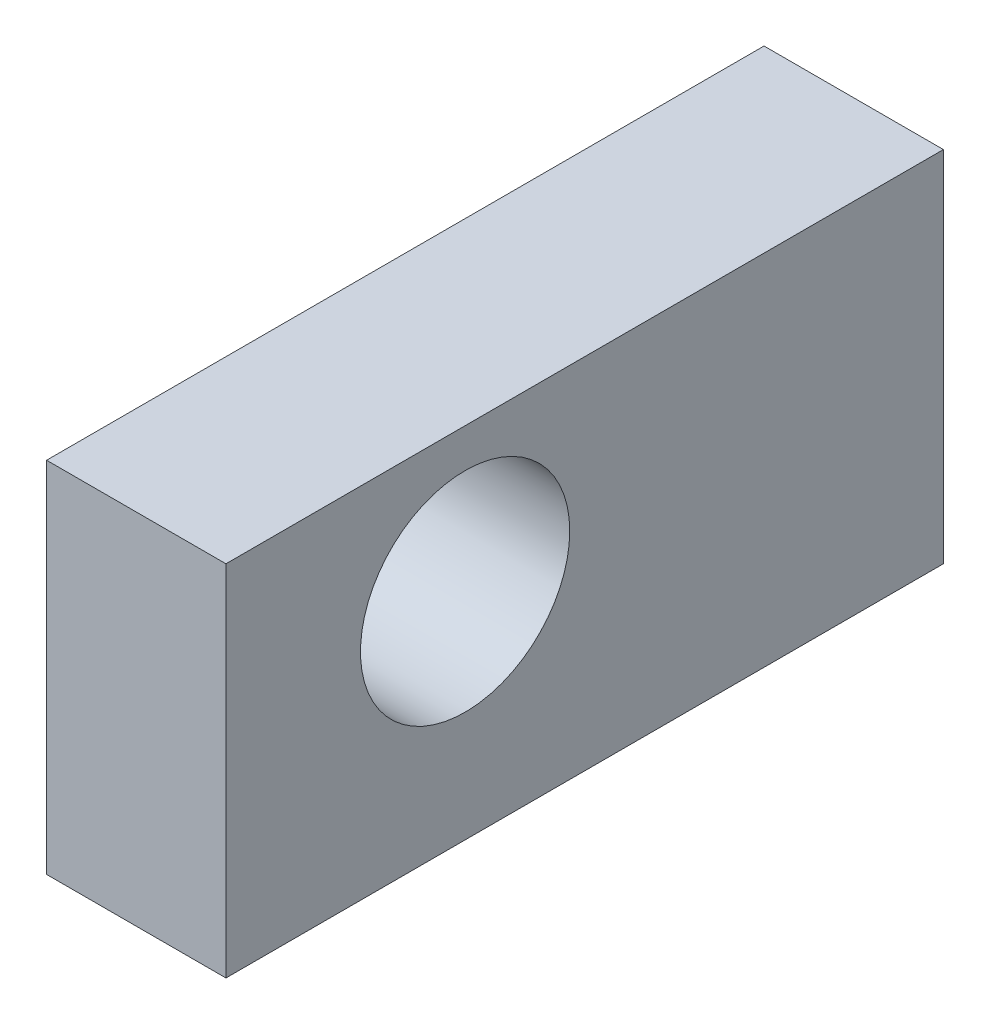
SolidWorks part; units mm, degrees
material "1060 Alloy"
ref_plane "Front Plane" through (0, 0, 0) normal (0, 0, 1) x (1, 0, 0)
ref_plane "Top Plane" through (0, 0, 0) normal (0, 1, 0) x (1, 0, 0)
ref_plane "Right Plane" through (0, 0, 0) normal (1, 0, 0) x (0, 0, -1)
sketch "Sketch1" plane through (0, 0, 0) normal (1, 0, 0) x (0, 0, -1)
  line L1 (-19.05, -9.525) -> (19.05, -9.525)
  line L2 (-19.05, -9.525) -> (-19.05, 9.525)
  line L3 (-19.05, 9.525) -> (19.05, 9.525)
  line L4 (19.05, -9.525) -> (19.05, 9.525)
  line L5 (-19.05, -9.525) -> (19.05, 9.525) construction
  line L6 (-19.05, 9.525) -> (19.05, -9.525) construction
  point P0 (0, 0)
  dimension "D1" = 38.1
  dimension "D2" = 19.05
extrude "Boss-Extrude1" add sketch "Sketch1" along normal blind 9.525
hole_wizard "7/16 (0.4375) Diameter Hole1" positions "Sketch9" profile "Sketch8" hole size "7/16" standard "ANSI Inch"
sketch "Sketch9" plane through (9.525, 0, 0) normal (1, 0, 0) x (0, 0, -1)
  line L0 (-19.05, -9.525) -> (19.05, -9.525) construction
  line L1 (19.05, -9.525) -> (19.05, 9.525) construction
  point P0 (-6.35, 1.905)
  dimension "D2" = 25.4
  dimension "D1" = 11.43
sketch "Sketch8" plane through (9.525, 1.905, 6.35) normal (0, 1, 0) x (0, 0, -1)
  line L0 (0, 0) -> (0, 73.4425)
  line L1 (0, 73.4425) -> (5.5562, 70.104)
  line L2 (5.5562, 70.104) -> (5.5562, 0)
  line L5 (5.5562, 0) -> (0, 0)
  line L10 (0, 73.4425) -> (-5.5563, 70.104) construction
  line L11 (0, -6.35) -> (0, 107.95) construction
  dimension "Hole Dia." = 11.1125
  dimension "Hole Depth" = 70.104
  dimension "Drill Angle" = 118
hole_wizard "#10-32 Tapped Hole1" positions "Sketch11" profile "Sketch10" tap size "#10-32" standard "ANSI Inch"
sketch "Sketch11" plane through (-1.1365, 0.5118, -19.05) normal (0, 0, -1) x (-1, 0, 0)
  line L0 (-10.6615, 9.0132) -> (-1.1365, 9.0132) construction
  line L2 (-10.6615, -10.0368) -> (-1.1365, -10.0368) construction
  line L3 (-10.6615, 9.0132) -> (-1.1365, 9.0132) construction
  point P0 (-5.899, -3.6868)
  point P2 (-5.899, 5.2032)
  point P6 (-5.899, 9.0132)
  dimension "D1" = 0
  dimension "D2" = 0
  dimension "D3" = 3.81
  dimension "D4" = 6.35
sketch "Sketch10" plane through (4.7625, -3.175, -19.05) normal (1, 0, 0) x (0, 1, 0)
  line L0 (0, 0) -> (0, 13.1513)
  line L1 (0, 13.1513) -> (2.0193, 11.938)
  line L2 (2.0193, 11.938) -> (2.0193, 0)
  line L5 (2.0193, 0) -> (0, 0)
  line L10 (0, 13.1513) -> (-2.0193, 11.938) construction
  line L11 (0, -6.35) -> (0, 107.95) construction
  dimension "Tap Drill Dia." = 4.0386
  dimension "Tap Drill Depth" = 11.938
  dimension "Drill Angle" = 118
cosmetic thread "Hole Thread1"
cosmetic thread "Hole Thread2"
